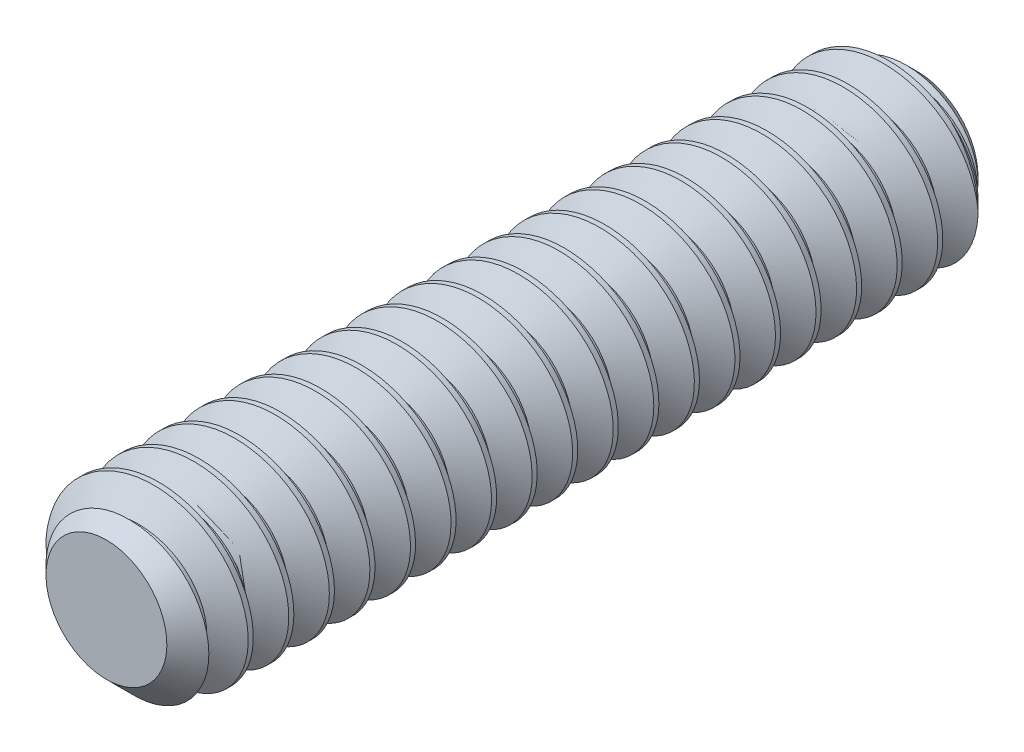
SolidWorks part; units mm, degrees
ref_plane "Front Plane" through (0, 0, 0) normal (0, 0, 1) x (1, 0, 0)
ref_plane "Top Plane" through (0, 0, 0) normal (0, 1, 0) x (1, 0, 0)
ref_plane "Right Plane" through (0, 0, 0) normal (1, 0, 0) x (0, 0, -1)
sketch "Sketch1" plane through (0, 0, 0) normal (1, 0, 0) x (0, 0, -1)
  line L0 (-6.35, -1.4224) -> (-6.35, 1.4224) construction
  line L1 (-6.35, 1.4224) -> (6.35, 1.4224) construction
  line L2 (-6.9453, 1.4911) -> (-6.6278, 0.9412) construction
  line L3 (-6.6278, 0.9412) -> (-6.3103, 1.4911) construction
  line L4 (-6.3103, 1.4911) -> (-6.9453, 1.4911) construction
  line L5 (-6.9056, 1.4224) -> (-6.35, 1.4224) construction
  line L6 (-6.6278, 1.4911) -> (-6.6278, 1.4224) construction
  line L7 (-6.6278, 1.4224) -> (-6.6278, 1.01) construction
  line L8 (-6.6278, 1.01) -> (-6.6278, 0.9412) construction
  line L9 (-6.6675, 1.01) -> (-6.5881, 1.01)
  line L10 (-6.9255, 1.4568) -> (-6.3302, 1.4568)
  line L11 (-6.5881, 1.01) -> (-6.3302, 1.4568)
  line L12 (-6.6675, 1.01) -> (-6.9255, 1.4568)
  line L13 (-6.35, 0.9462) -> (-5.8738, 1.4224) construction
  line L14 (0, 1.4224) -> (0, -1.4224) construction
  point P2 (0, 1.4224)
  point P6 (-6.35, 0)
  point P18 (-6.6278, 1.4568)
  point P26 (-4.7625, -1.4224)
  dimension "Length" = 12.7
  dimension "Thread Size" = 2.8448
  dimension "Thread Pitch" = 0.635
  dimension "D2" = 0.0794
  dimension "D1" = 45
  dimension "D3" = 0.4763
  dimension "D5" = 1.5875
sketch "Sketch2" plane through (0, 0, 0) normal (0, 0, 1) x (1, 0, 0)
  circle A0 centre (0, 0) radius 1.4224
sketch "Sketch3" plane through (0, 0, 0) normal (1, 0, 0) x (0, 0, -1)
  line L0 (-6.35, 0) -> (-6.35, 0.9462)
  line L1 (-6.35, 0.9462) -> (-5.8738, 1.4224)
  line L2 (-5.8738, 1.4224) -> (5.8738, 1.4224)
  line L3 (0, 1.4224) -> (0, 0) construction
  line L4 (6.35, 0) -> (-6.35, 0)
  line L5 (0, 1.4224) -> (0, -1.4224) construction
  line L6 (6.35, 0.9462) -> (5.8738, 1.4224)
  line L7 (6.35, 0) -> (6.35, 0.9462)
revolve "Revolve1" add sketch "Sketch3" angle 360 about L4
sketch "Sketch4" plane through (0, 0, 6.35) normal (0, 0, 1) x (1, 0, 0)
  circle A0 centre (0, 0) radius 1.4224 construction
  circle A1 centre (0, 0) radius 1.4224
curve "Helix/Spiral1" pitch 0.635 height 13.335 radius 1.4224 centre (0, 0, 6.35) axis (0, 0, -1) start towards (0, 1, 0)
sketch "Sketch5" plane through (0, 0, 0) normal (1, 0, 0) x (0, 0, -1)
  line L0 (-6.6675, 1.01) -> (-6.5881, 1.01) construction
  line L1 (-6.5881, 1.01) -> (-6.3302, 1.4568) construction
  line L2 (-6.9255, 1.4568) -> (-6.3302, 1.4568) construction
  line L3 (-6.6675, 1.01) -> (-6.9255, 1.4568) construction
  line L4 (-6.6675, 1.01) -> (-6.5881, 1.01)
  line L5 (-6.5881, 1.01) -> (-6.3302, 1.4568)
  line L6 (-6.9255, 1.4568) -> (-6.3302, 1.4568)
  line L7 (-6.6675, 1.01) -> (-6.9255, 1.4568)
sweep "Cut-Sweep1" cut profiles "Sketch5" path "Helix/Spiral1"
equation "\"D2@Sketch1\" = \"Thread Pitch@Sketch1\" / 8"
equation "\"D3@Sketch1\"=\"Thread Pitch@Sketch1\"*.75"
equation "\"D3@Helix/Spiral1\"=\"Length@Sketch1\"+\"Thread Pitch@Sketch1\""
equation "\"D4@Helix/Spiral1\"=\"Thread Pitch@Sketch1\""
equation "\"D5@Sketch1\"=\"Thread Pitch@Sketch1\"*2.5"
